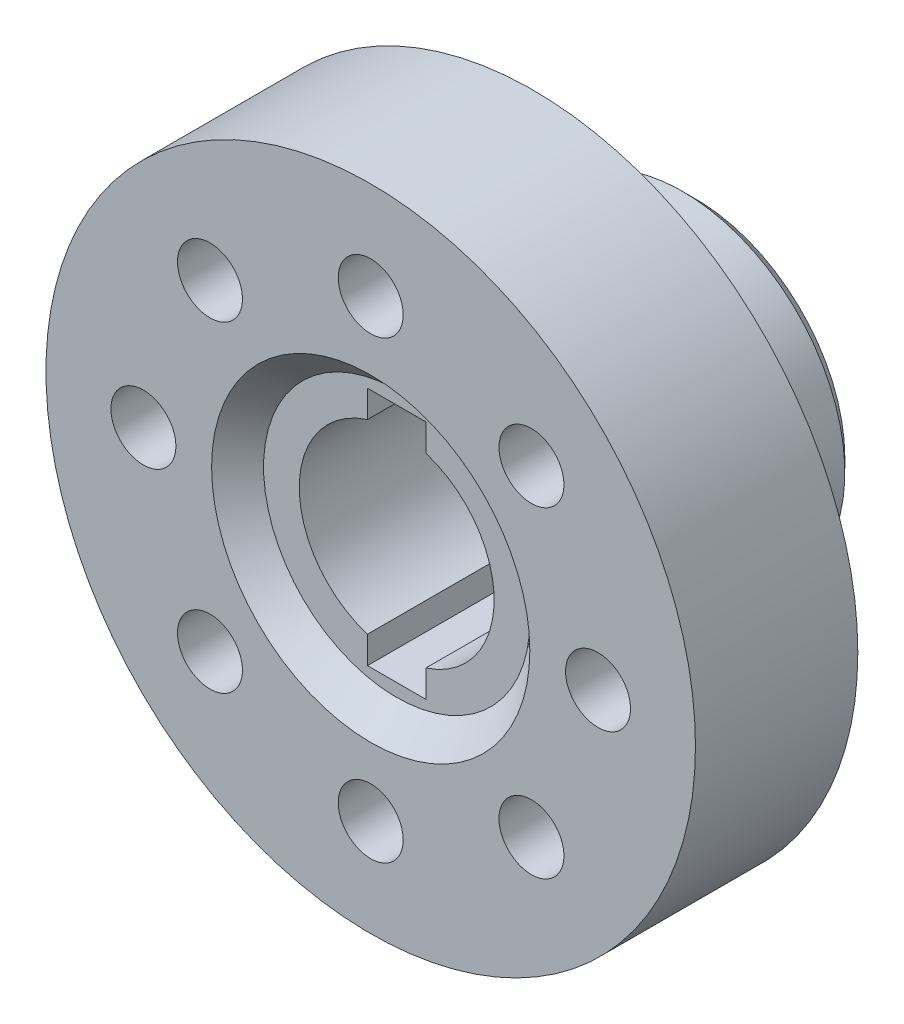
SolidWorks part; units mm, degrees
ref_plane "Front Plane" through (0, 0, 0) normal (0, 0, 1) x (1, 0, 0)
ref_plane "Top Plane" through (0, 0, 0) normal (0, 1, 0) x (1, 0, 0)
ref_plane "Right Plane" through (0, 0, 0) normal (1, 0, 0) x (0, 0, -1)
sketch "Sketch1" plane through (0, 0, 0) normal (0, 0, 1) x (1, 0, 0)
  circle A0 centre (0, 0) radius 50
  dimension "D1" = 100
extrude "Boss-Extrude1" add sketch "Sketch1" against normal blind 25
hole_wizard "CBORE for M10 Hex Head Bolt1" positions "Sketch2" profile "Sketch3" counterbore size "M10" standard "ANSI Metric" end condition through all
sketch "Sketch2" plane through (0, 0, -25) normal (0, 0, -1) x (-1, 0, 0)
  line L0 (0, 35) -> (0, 0) construction
  line L1 (0, 0) -> (24.7487, 24.7487) construction
  circle A0 centre (0, 0) radius 35 construction
  point P5 (0, 35)
  point P19 (24.7487, 24.7487)
  point P20 (35, 0)
  point P21 (24.7487, -24.7487)
  point P22 (0, -35)
  point P23 (-24.7487, -24.7487)
  point P24 (-35, 0)
  point P25 (-24.7487, 24.7487)
  dimension "D1" = 70
  dimension "D3" = 45
  dimension "D2" = 8
sketch "Sketch3" plane through (24.7487, 24.7487, -25) normal (1, 0, 0) x (0, 1, 0)
  line L0 (0, 0) -> (0, 25)
  line L1 (0, 25) -> (5, 25)
  line L3 (5, 25) -> (5, 12.5)
  line L4 (5, 12.5) -> (10, 12.5)
  line L5 (10, 12.5) -> (10, 0)
  line L7 (10, 0) -> (0, 0)
  line L11 (0, -6.35) -> (0, 107.95) construction
  dimension "Thru Hole Dia." = 10
  dimension "Thru Hole Depth" = 25
  dimension "C'Bore Dia." = 20
  dimension "C'Bore Depth" = 12.5
sketch "Sketch5" plane through (0, 0, -25) normal (0, 0, -1) x (-1, 0, 0)
  circle A0 centre (0, 0) radius 25
  dimension "D1" = 50
extrude "Boss-Extrude2" add sketch "Sketch5" along normal blind 25
chamfer "Chamfer1" distance 2 angle 45 8 edges at (-34.7487, -24.7487, -25) (-10, -35, -25) (14.7487, -24.7487, -25) (25, 0, -25) (14.7487, 24.7487, -25) (-10, 35, -25) (-34.7487, 24.7487, -25) (-45, 0, -25)
sketch "Sketch8" plane through (0, 0, 0) normal (0, 0, 1) x (1, 0, 0)
  line L0 (-4.5, 14.3091) -> (-4.5, 18.5)
  line L1 (4.5, -18.5) -> (-4.5, -18.5)
  line L2 (4.5, -18.5) -> (4.5, -14.3091)
  line L3 (4.5, 18.5) -> (-4.5, 18.5)
  line L4 (-4.5, -18.5) -> (-4.5, -14.3091)
  line L9 (4.5, 14.3091) -> (4.5, 18.5)
  arc A0 (-4.5, 14.3091) -> (-4.5, -14.3091) centre (0, 0) ccw
  arc A1 (4.5, -14.3091) -> (4.5, 14.3091) centre (0, 0) ccw
  point P1 (0, 18.5)
  dimension "D1" = 30
  dimension "D2" = 37
  dimension "D3" = 9
  dimension "D4" = 4.1909
extrude "Cut-Extrude1" cut sketch "Sketch8" against normal through all
sketch "Sketch9" plane through (0, 0, 0) normal (0, 0, 1) x (1, 0, 0)
  circle A0 centre (0, 0) radius 24.5
  dimension "D1" = 49
extrude "Cut-Extrude2" cut sketch "Sketch9" against normal blind 4
chamfer "Chamfer2" distance 4 angle 45 1 edges at (24.5, 0, -4)
chamfer "Chamfer3" distance 2 angle 45 1 edges at (-25, 0, -50)
